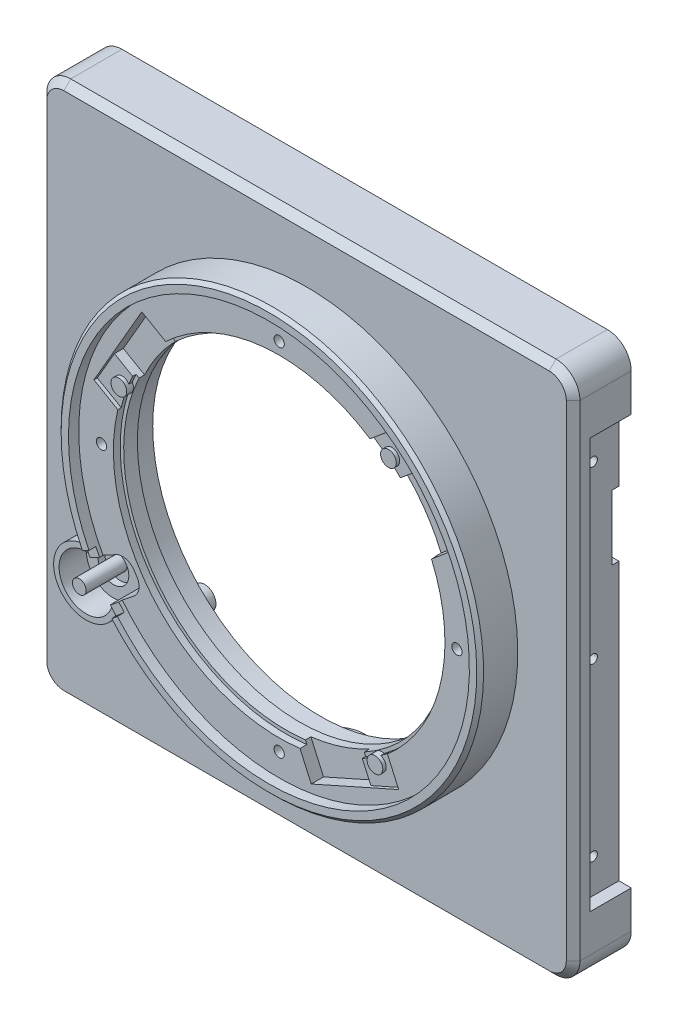
SolidWorks part; units mm, degrees
ref_plane "前视基准面" through (0, 0, 0) normal (0, 0, 1) x (1, 0, 0)
ref_plane "上视基准面" through (0, 0, 0) normal (0, 1, 0) x (1, 0, 0)
ref_plane "右视基准面" through (0, 0, 0) normal (1, 0, 0) x (0, 0, -1)
other "Configuration Table"
sketch "草图1" plane through (0, 0, 0) normal (0, 0, 1) x (1, 0, 0)
  line L1 (-39, -39) -> (39, -39)
  line L2 (-39, -39) -> (-39, 39)
  line L3 (-39, 39) -> (39, 39)
  line L4 (39, -39) -> (39, 39)
  line L5 (-39, -39) -> (39, 39) construction
  line L6 (-39, 39) -> (39, -39) construction
  circle A0 centre (0, 0) radius 23.75
  point P0 (0, 0)
  dimension "D2" = 47.5
  dimension "D1" = 78
extrude "凸台-拉伸1" add sketch "草图1" against normal blind 2
sketch "草图2" plane through (0, 0, 0) normal (0, 0, 1) x (1, 0, 0)
  circle A0 centre (0, 0) radius 23.75
  circle A1 centre (0, 0) radius 23.75 construction
  circle A2 centre (0, 0) radius 30.9
  dimension "D1" = 61.8
extrude "凸台-拉伸2" add sketch "草图2" along normal blind 4
sketch "草图3" plane through (0, 0, -2) normal (0, 0, -1) x (-1, 0, 0)
  line L1 (-39, -39) -> (39, -39)
  line L2 (-39, -39) -> (-39, 39)
  line L3 (-39, 39) -> (39, 39)
  line L4 (39, -39) -> (39, 39)
  line L5 (-39, -39) -> (39, 39) construction
  line L6 (-39, 39) -> (39, -39) construction
  line L7 (-37, -37) -> (37, -37)
  line L8 (-37, -37) -> (-37, 37)
  line L9 (-37, 37) -> (37, 37)
  line L10 (37, -37) -> (37, 37)
  line L11 (-37, -37) -> (37, 37) construction
  line L12 (-37, 37) -> (37, -37) construction
  line L13 (-37, 37) -> (-32, 37)
  line L14 (-37, 37) -> (-37, 32)
  line L15 (-37, 32) -> (-32, 32)
  line L16 (-32, 37) -> (-32, 32)
  line L17 (37, 37) -> (32, 37)
  line L18 (37, 37) -> (37, 32)
  line L19 (37, 32) -> (32, 32)
  line L20 (32, 37) -> (32, 32)
  line L21 (-37, -37) -> (-32, -37)
  line L22 (-37, -37) -> (-37, -32)
  line L23 (-37, -32) -> (-32, -32)
  line L24 (-32, -37) -> (-32, -32)
  line L25 (37, -37) -> (32, -37)
  line L26 (37, -37) -> (37, -32)
  line L27 (37, -32) -> (32, -32)
  line L28 (32, -37) -> (32, -32)
  line L29 (-35.5, 32) -> (-35.5, -32)
  point P0 (0, 0)
  point P7 (0, 0)
  line M23 (-39, 39) -> (-39, -39)
  line M24 (-39, -39) -> (39, -39)
  line M25 (39, -39) -> (39, 39)
  line M26 (39, 39) -> (-39, 39)
  dimension "D1" = 2
  dimension "D2" = 5
  dimension "D4" = 1.5
extrude "凸台-拉伸3" add sketch "草图3" along normal blind 6.5 contours L10 L7 L8 L9 M26 M23 M24 M25 | L16 L9 L8 L15 | L29 L15 L8 L23 | L7 L24 L23 L8 | L28 L7 L10 L27 | L9 L20 L19 L10 region at (37.8969, 0, -2) region at (34.5, -34.5, -2) region at (36.25, 0, -2) region at (-34.5, -34.5, -2) region at (34.5, 34.5, -2) region at (-34.5, 34.5, -2)
sketch "草图4" plane through (0, 0, 4) normal (0, 0, 1) x (1, 0, 0)
  line L0 (0, 26) -> (0, -26) construction
  line L1 (-26, 0) -> (26, 0) construction
  circle A0 centre (0, 0) radius 26 construction
  circle A1 centre (0, 26) radius 0.75
  circle A2 centre (26, 0) radius 0.75
  circle A3 centre (0, -26) radius 0.75
  circle A4 centre (-26, 0) radius 0.75
  dimension "D2" = 52
  dimension "D3" = 1.5
extrude "切除-拉伸1" cut sketch "草图4" against normal blind 5
sketch "草图5" plane through (0, 0, 4) normal (0, 0, 1) x (1, 0, 0)
  line L0 (-15.4397, 0) -> (13.8511, 0) construction
  line L1 (-27.9748, -13.7193) -> (-23.5593, -20.3904)
  line L2 (-23.5593, -20.3904) -> (0, 0) construction
  line L3 (0, 0) -> (-27.9748, -13.7193) construction
  line L4 (-25.7671, -17.0549) -> (0, 0) construction
  line L5 (-27.9748, -13.7193) -> (-26.8884, -13.1865)
  line L6 (-26.8884, -13.1865) -> (-26.2006, -14.2257)
  line L7 (-26.2006, -14.2257) -> (0, 0) construction
  line L8 (0, 0) -> (-23.3322, -18.5593) construction
  line L9 (-23.3322, -18.5593) -> (-22.6444, -19.5985)
  line L10 (-22.6444, -19.5985) -> (-23.5593, -20.3904)
  line L11 (-26.2006, -14.2257) -> (-23.8565, -12.953)
  line L12 (-21.2344, -13.6068) -> (-20.822, -14.2298)
  line L13 (-21.2448, -16.8989) -> (-23.3322, -18.5593)
  circle A0 centre (0, 0) radius 30.9 construction
  arc A1 (-20.822, -14.2298) -> (-21.2448, -16.8989) centre (-22.4898, -15.3336) cw
  arc A2 (-23.8565, -12.953) -> (-21.2344, -13.6068) centre (-22.9021, -14.7106) cw
  point P17 (-19.8105, -15.758)
  point P20 (-22.2459, -12.0785)
  dimension "D6" = 2
  dimension "D1" = 33.5
  dimension "D2" = 8
  dimension "D3" = 5
  dimension "D4" = 1.2
  dimension "D5" = 4.5
extrude "切除-拉伸2" cut sketch "草图5" against normal blind 4
sketch "草图8" plane through (0, 0, 4) normal (0, 0, 1) x (1, 0, 0)
  line L0 (-27.7433, -13.6058) -> (-26.3292, -12.9123)
  line L1 (-23.3644, -20.2217) -> (-22.1735, -19.191)
  circle A0 centre (0, 0) radius 30.9
  circle A1 centre (0, 0) radius 29.325
  arc A2 (-23.3644, -20.2217) -> (-27.7433, -13.6058) centre (0, 0) ccw construction
  line M27 (-27.7433, -13.6058) -> (-26.8884, -13.1865)
  line M35 (-22.6444, -19.5985) -> (-23.3644, -20.2217)
  arc M36 (-23.3644, -20.2217) -> (-27.7433, -13.6058) centre (0, 0) ccw
  dimension "D1" = 58.65
extrude "凸台-拉伸5" add sketch "草图8" along normal blind 1.5 contours A1 L1 L0 M35 M36 M27 region at (-6.7861, 29.2491, 4)
chamfer "倒角1" distance 0.5 angle 45 1 edges at (25.7671, 17.0549, 5.5)
sketch "草图9" plane through (0, 0, -2) normal (0, 0, -1) x (-1, 0, 0)
  line L1 (-19, -20) -> (19, -20) construction
  line L2 (-19, -20) -> (-19, 20) construction
  line L3 (-19, 20) -> (19, 20) construction
  line L4 (19, -20) -> (19, 20) construction
  line L5 (-19, -20) -> (19, 20) construction
  line L6 (-19, 20) -> (19, -20) construction
  circle A0 centre (-19, -20) radius 0.8
  circle A1 centre (-19, -20) radius 1.65
  circle A4 centre (19, 20) radius 0.8
  circle A5 centre (19, 20) radius 1.65
  circle A6 centre (19, -20) radius 0.8
  circle A7 centre (19, -20) radius 1.65
  point P0 (0, 0)
  dimension "D2" = 1.6
  dimension "D3" = 3.3
  dimension "D1" = 38
  dimension "D4" = 40
extrude "凸台-拉伸6" add sketch "草图9" along normal blind 2.1
extrude "切除-拉伸4" cut sketch "草图9<2>" against normal blind 2 contours A4 | A0 | A6 region at (19, -20, -2) region at (-19, 20, -2) region at (-19, -20, -2)
sketch "草图9<2>" plane through (0, 0, -2) normal (0, 0, -1) x (-1, 0, 0) same geometry as "草图9"
sketch "草图10" plane through (0, 0, -8.5) normal (0, 0, -1) x (-1, 0, 0)
  line L0 (39, 39) -> (-39, 39) construction
  line L1 (34.5, -34.5) -> (-34.5, -34.5) construction
  line L2 (34.5, -34.5) -> (34.5, 34.5) construction
  line L3 (34.5, 34.5) -> (-34.5, 34.5) construction
  line L4 (-34.5, -34.5) -> (-34.5, 34.5) construction
  line L5 (34.5, -34.5) -> (-34.5, 34.5) construction
  line L6 (34.5, 34.5) -> (-34.5, -34.5) construction
  circle A0 centre (-34.5, 34.5) radius 0.8
  circle A1 centre (34.5, 34.5) radius 0.8
  circle A2 centre (34.5, -34.5) radius 0.8
  circle A3 centre (-34.5, -34.5) radius 0.8
  point P0 (0, 0)
  dimension "D2" = 1.6
  dimension "D1" = 4.5
extrude "切除-拉伸5" cut sketch "草图10" against normal blind 4
sketch "草图18" plane through (0, -39, 0) normal (0, -1, 0) x (1, 0, 0)
  line L0 (39, -8.5) -> (-39, -8.5) construction
  line L1 (-39, 0) -> (39, 0) construction
  circle A0 centre (0, -4.25) radius 4.25
  circle A1 centre (0, -4.25) radius 2.5527
  dimension "D1" = 5.1054
extrude "凸台-拉伸9" add sketch "草图18" against normal blind 9 contours A1 | A0 A1 region at (-4.1298, -39, -4.25) region at (0, -39, -4.25)
extrude "切除-拉伸9" cut sketch "草图18<4>" against normal blind 7.5 contours A1 region at (0, -39, -4.25)
sketch "草图18<4>" plane through (0, -39, 0) normal (0, -1, 0) x (1, 0, 0) same geometry as "草图18"
sketch "草图30" plane through (0, 0, 0) normal (0, 0, 1) x (1, 0, 0)
  line L0 (-22.39, -14.8196) -> (0, 0) construction
  line L1 (-26.8884, -13.1865) -> (-28.4451, -13.9499)
  line L2 (-26.2006, -14.2257) -> (-27.3486, -14.8491)
  line L3 (-23.3322, -18.5593) -> (-24.3546, -19.3725)
  line L4 (-22.6444, -19.5985) -> (-23.9553, -20.7332)
  line L5 (-22.6444, -19.5985) -> (-23.3322, -18.5593)
  line L6 (-23.3644, -20.2217) -> (-22.6444, -19.5985) construction
  line L7 (-23.3322, -18.5593) -> (-21.2448, -16.8989) construction
  line L8 (-23.8565, -12.953) -> (-26.2006, -14.2257) construction
  line L9 (-27.2944, -13.3856) -> (-26.3292, -12.9123) construction
  line L10 (-26.8884, -13.1865) -> (-26.2006, -14.2257)
  line L11 (-20.822, -14.2298) -> (-21.2344, -13.6068) construction
  line L12 (-20.822, -14.2298) -> (-21.2344, -13.6068) construction
  circle A0 centre (-28.2462, -18.6958) radius 4.75
  circle A2 centre (-28.2462, -18.6958) radius 3.95
  point P3 (-21.0282, -13.9183)
  line M13 (-26.8884, -13.1865) -> (-27.7433, -13.6058)
  line M15 (-23.3644, -20.2217) -> (-22.6444, -19.5985)
  line M16 (-22.6444, -19.5985) -> (-23.3322, -18.5593)
  line M22 (-26.2006, -14.2257) -> (-26.8884, -13.1865)
  dimension "D2" = 9.5
  dimension "D3" = 7.9
  dimension "D1" = 33.873
extrude "凸台-拉伸10" add sketch "草图30" along normal blind 4 contours A0 L2 L1 M22 M13 | A0 L0 A2 L2 | L0 A0 L3 A2 | A0 L4 L3 M15 M16 region at (-27.1202, -13.7897, 0) region at (-27.418, -14.155, 0) region at (-23.2902, -19.5762, 0)
sketch "草图31" plane through (0, 0, 0) normal (0, 0, 1) x (1, 0, 0)
  circle A0 centre (-28.2462, -18.6958) radius 1
  circle A1 centre (-28.2462, -18.6958) radius 2.25
  dimension "D1" = 2
  dimension "D2" = 4.5
extrude "切除-拉伸19" cut sketch "草图31" against normal blind 1
sketch "草图32" plane through (0, 0, 0) normal (0, 0, 1) x (1, 0, 0)
  circle A0 centre (-28.2462, -18.6958) radius 1
  circle A1 centre (-28.2462, -18.6958) radius 1 construction
extrude "凸台-拉伸11" add sketch "草图32" along normal blind 5
sketch "草图33" plane through (0, 0, 4) normal (0, 0, 1) x (1, 0, 0)
  line L0 (-26.3292, -12.9123) -> (-27.7433, -13.6058)
  line L1 (-27.1554, -14.7442) -> (-25.7713, -13.9927)
  line L2 (-23.8565, -12.953) -> (-27.3486, -14.8491) construction
  line L3 (-23.8565, -12.953) -> (-27.3486, -14.8491) construction
  line L4 (-24.1826, -19.2357) -> (-22.95, -18.2552)
  line L5 (-24.3546, -19.3725) -> (-21.2448, -16.8989) construction
  line L6 (-22.1735, -19.191) -> (-23.3644, -20.2217)
  circle A0 centre (0, 0) radius 29.325
  circle A1 centre (0, 0) radius 30.9
  line M3 (-26.3292, -12.9123) -> (-27.7433, -13.6058)
  line M7 (-23.3644, -20.2217) -> (-22.1735, -19.191)
  line M10 (-27.3486, -14.8491) -> (-23.8565, -12.953)
  line M14 (-21.2448, -16.8989) -> (-24.3546, -19.3725)
extrude "凸台-拉伸12" add sketch "草图33" along normal blind 0.5 contours A1 A0 M3 M10 | A1 A0 M14 M7 region at (-26.7598, -13.8189, 4) region at (-23.1762, -19.233, 4)
fillet "圆角5" radius 1 2 edges at (-3.6056, -33.5, -2) (3.6056, -33.5, -2)
fillet "圆角2" radius 1.5 12 edges at (32, -37, -5.25) (-32, -37, -5.25) (-32, -32, -5.25) (-37, -32, -5.25) (-37, 32, -5.25) (-32, 37, -5.25) (32, -32, -5.25) (-32, 32, -5.25) (32, 37, -5.25) (32, 32, -5.25) (35.5, 32, -5.25) (35.5, -32, -5.25)
fillet "圆角3" radius 3.5 4 edges at (39, -39, -4.25) (-39, -39, -4.25) (-39, 39, -4.25) (39, 39, -4.25)
chamfer "倒角2" distance 1 angle 45 8 edges at (0, -39, 0) (37.9749, -37.9749, 0) (-37.9749, -37.9749, 0) (39, 0, 0) (-39, 0, 0) (37.9749, 37.9749, 0) (-37.9749, 37.9749, 0) (0, 39, 0)
sketch "草图11" plane through (0, 0, 4) normal (0, 0, 1) x (1, 0, 0)
  circle A0 centre (0, 0) radius 24.25
  dimension "D1" = 48.5
extrude "切除-拉伸6" cut sketch "草图11" against normal blind 1
sketch "草图19" plane through (39, 0, 0) normal (-1, 0, 0) x (0, 0, 1)
  line L0 (-8.5, -35.5) -> (-8.5, 35.5) construction
  line L1 (-8.5, 30) -> (-2.5, 30)
  line L2 (-8.5, 30) -> (-8.5, -30)
  line L3 (-8.5, -30) -> (-2.5, -30)
  line L4 (-2.5, 30) -> (-2.5, -30)
  line L5 (-10.4781, 0) -> (-27.7758, 0) construction
  dimension "D1" = 6
  dimension "D2" = 60
extrude "切除-拉伸10" cut sketch "草图19" along normal blind 1.8
sketch "草图12" plane through (0, 0, -8.5) normal (0, 0, -1) x (-1, 0, 0)
  line L0 (-30.5, 37) -> (30.5, 37) construction
  line L1 (-14.5, 37) -> (14.5, 37)
  line L2 (-14.5, 37) -> (-14.5, 38)
  line L3 (-14.5, 38) -> (14.5, 38)
  line L4 (14.5, 37) -> (14.5, 38)
  line L10 (-30.5, -37) -> (-5.099, -37) construction
  line L11 (14.5, -37) -> (-14.5, -37)
  line L12 (14.5, -37) -> (14.5, -38)
  line L13 (14.5, -38) -> (-14.5, -38)
  line L14 (-14.5, -37) -> (-14.5, -38)
  line L20 (0, -4.6052) -> (0, 11.8131) construction
  line L21 (9.1859, 0) -> (-14.9207, 0) construction
  line L22 (-3.5, -37) -> (-3.5, -38)
  line L23 (3.5, -37) -> (3.5, -38)
  line M27 (30.5, -37) -> (0, -37)
  line M39 (-30.5, 37) -> (30.5, 37)
  dimension "D1" = 29
  dimension "D2" = 1
  dimension "D3" = 7
extrude "切除-拉伸7" cut sketch "草图12" against normal blind 1 contours L22 L11 L14 L13 | L23 L13 L12 M27 | L4 L3 L2 M39
sketch "草图21" plane through (0, 0, -2) normal (0, 0, -1) x (-1, 0, 0)
  circle A0 centre (0, 0) radius 24.5
  dimension "D1" = 49
extrude "切除-拉伸12" cut sketch "草图21" against normal blind 3
sketch "草图22" plane through (0, 0, 0) normal (0, 0, 1) x (1, 0, 0)
  text T0 "Sitina" font "Corbel" height 3.5
  text T1 "S1" font "Sylfaen" height 3.5
sketch "草图23" plane through (0, 0, -8.5) normal (0, 0, -1) x (-1, 0, 0)
  line L1 (-35.5, 20) -> (-37.2, 20)
  line L2 (-35.5, 20) -> (-35.5, 10.5)
  line L3 (-35.5, 10.5) -> (-37.2, 10.5)
  line L4 (-37.2, 20) -> (-37.2, 10.5)
  line L5 (-37.2, -30) -> (-37.2, 30) construction
  line L6 (-35.5, 30.5) -> (-35.5, -30.5) construction
  dimension "D1" = 9.5
  dimension "D2" = 10.5
extrude "切除-拉伸14" cut sketch "草图23" against normal blind 1
sketch "草图24" plane through (37.2, 0, 0) normal (1, 0, 0) x (0, 0, -1)
  line L0 (4.7, -23.516) -> (4.7, -0.4558) construction
  line L3 (4.7, -25) -> (4.7, 0) construction
  line L4 (8.5, -30) -> (8.5, -35.5) construction
  line L5 (8.5, -39) -> (1, -39) construction
  circle A0 centre (4.7, -25) radius 0.65
  circle A1 centre (4.7, 0) radius 0.65
  circle A2 centre (4.7, 25) radius 0.65
  point P6 (8.5, -32.75)
  dimension "D2" = 1.3
  dimension "D1" = 3.8
  dimension "D3" = 14
  dimension "D5" = 25
  dimension "D4" = 3
extrude "切除-拉伸15" cut sketch "草图24" against normal blind 4.75
sketch "草图26" plane through (-39, 0, 0) normal (1, 0, 0) x (0, 0, -1)
  line L0 (8.5, 35.5) -> (8.5, 30) construction
  line L1 (5.8, -30) -> (7.2, -30)
  line L2 (5.8, -30) -> (5.8, -18.5)
  line L3 (5.8, -18.5) -> (7.2, -18.5)
  line L4 (7.2, -30) -> (7.2, -18.5)
  line L5 (1, -35.5) -> (8.5, -35.5) construction
  line L6 (12.7, 2.7) -> (7.7, 2.7) construction
  line L7 (12.7, 0.6) -> (7.7, 0.6)
  line L8 (12.7, 4.8) -> (7.7, 4.8)
  line L9 (8.5, 29.5) -> (8.5, 20.4)
  line L12 (8.5, 35.5) -> (1, 35.5) construction
  line L13 (8.5, 20.4) -> (6.3, 20.4)
  line L14 (8.5, 29.5) -> (6.3, 29.5)
  line L15 (5.1, 28.3) -> (5.1, 21.6)
  line L17 (8.5, 14) -> (5.1, 14)
  line L18 (8.5, 14) -> (8.5, 6)
  line L19 (8.5, 6) -> (5.1, 6)
  line L20 (5.1, 14) -> (5.1, 6)
  circle A0 centre (9, -10.2) radius 4.25
  arc A1 (12.7, 0.6) -> (12.7, 4.8) centre (12.7, 2.7) ccw
  arc A2 (7.7, 4.8) -> (7.7, 0.6) centre (7.7, 2.7) ccw
  arc A5 (6.3, 29.5) -> (5.1, 28.3) centre (6.3, 28.3) ccw
  arc A6 (6.3, 20.4) -> (5.1, 21.6) centre (6.3, 21.6) cw
  point P10 (10.2, 2.7)
  dimension "D7" = 8.5
  dimension "D9" = 2.1
  dimension "D15" = 1.2
  dimension "D1" = 11.5
  dimension "D2" = 1.4
  dimension "D3" = 1.3
  dimension "D4" = 5.5
  dimension "D5" = 25.3
  dimension "D6" = 0.5
  dimension "D8" = 38.2
  dimension "D10" = 0.8
  dimension "D11" = 5
  dimension "D12" = 6
  dimension "D13" = 9.1
  dimension "D14" = 3.4
  dimension "D16" = 21.5
  dimension "D17" = 8
  dimension "D18" = 3.4
extrude "切除-拉伸17" cut sketch "草图26" along normal blind 10
sketch "草图29" plane through (0, 0, -2) normal (0, 0, -1) x (-1, 0, 0)
  line L0 (0, 6.6658) -> (0, 18.0542) construction
  line L1 (6.3625, 0) -> (19.1145, 0) construction
  circle A0 centre (-15, 22) radius 0.8
  circle A1 centre (15, -22) radius 0.8
  dimension "D1" = 1.6
  dimension "D2" = 15
  dimension "D3" = 15
  dimension "D4" = 22
  dimension "D5" = 22
extrude "切除-拉伸18" cut sketch "草图29" against normal blind 3
fillet "圆角6" radius 0.5 2 edges at (-27.7433, -13.6058, 2) (-23.3644, -20.2217, 2)
sketch "草图34" plane through (0, 0, 4) normal (0, 0, 1) x (1, 0, 0)
  line L0 (15.2413, -17.0225) -> (2.4517, -22.7168)
  line L1 (2.4517, -22.7168) -> (4.6888, -27.7413)
  line L2 (4.6888, -27.7413) -> (17.4784, -22.047)
  line L3 (17.4784, -22.047) -> (15.2413, -17.0225)
  line L4 (0, -1000) -> (0, 49000) construction
  line L5 (0, 0) -> (8.8465, -19.8696) construction
  line L6 (10.6736, -19.0561) -> (12.9107, -24.0806)
  line L7 (12.162, 19.3429) -> (21.161, 8.6183)
  line L8 (21.161, 8.6183) -> (25.3742, 12.1537)
  line L9 (25.3742, 12.1537) -> (16.3752, 22.8783)
  line L10 (16.3752, 22.8783) -> (12.162, 19.3429)
  line L11 (-15.3361, 16.9372) -> (-22.3361, 4.8128)
  line L12 (-22.3361, 4.8128) -> (-27.0992, 7.5628)
  line L13 (-27.0992, 7.5628) -> (-20.0992, 19.6872)
  line L14 (-20.0992, 19.6872) -> (-15.3361, 16.9372)
  line L15 (-24.5992, 11.8929) -> (-19.8361, 9.1429)
  line L16 (15.3759, 15.5127) -> (19.5891, 19.0481)
  line L17 (-18.8361, 10.875) -> (0, 0)
  line L18 (0, 0) -> (16.6615, 13.9806)
  circle A0 centre (0, 0) radius 21.75 construction
  point P5 (8.8465, -19.8696)
  point P19 (-18.8361, 10.875)
  point P22 (16.6615, 13.9806)
  circle M8 centre (0, 0) radius 24.25
  dimension "D1" = 43.5
  dimension "D2" = 14
  dimension "D3" = 5.5
  dimension "D4" = 24
  dimension "D5" = 5
  dimension "D6" = 5
  dimension "D7" = 5
  dimension "D8" = 60
  dimension "D9" = 50
extrude "切除-拉伸20" cut sketch "草图34" against normal blind 0.5 contours L6 L2 L3 M8 | L0 L6 L3 M8 | L16 L9 L10 M8 | L7 L16 L10 M8 | L15 L13 L12 M8 | L15 L12 L11 M8 region at (13.2013, -19.0643, 4) region at (14.5891, -21.424, 4) region at (-21.8858, 7.6638, 4) region at (-24.3955, 8.7571, 4) region at (16.5728, 19.9292, 4) region at (14.687, 17.9447, 4)
extrude "切除-拉伸21" cut sketch "草图34<3>" against normal blind 1.8 contours L6 L0 L1 M8 | L6 L1 L2 M8 | L13 L15 L14 M8 | L15 L11 L14 M8 | L16 L8 L9 M8 | L16 L7 L8 M8 region at (7.314, -21.7939, 4) region at (7.9313, -24.492, 4) region at (21.357, 14.375, 4) region at (18.9336, 13.0379, 4) region at (-18.7273, 13.3326, 4) region at (-20.8126, 15.1525, 4)
sketch "草图34<3>" plane through (0, 0, 4) normal (0, 0, 1) x (1, 0, 0) same geometry as "草图34"
sketch "草图35" plane through (0, 0, 3) normal (0, 0, 1) x (1, 0, 0)
  line L0 (17.4784, -22.047) -> (15.8383, -18.3633) construction
  line L1 (12.9107, -24.0806) -> (17.4784, -22.047) construction
  line L2 (25.3742, 12.1537) -> (16.3752, 22.8783) construction
  line L3 (-27.0992, 7.5628) -> (-20.0992, 19.6872) construction
  line L4 (-23.6071, 5.5467) -> (-27.0992, 7.5628) construction
  line L5 (16.3752, 22.8783) -> (13.2863, 20.2864) construction
  circle A0 centre (14.005, -20.6379) radius 1.15
  circle A1 centre (15.9781, 19.151) radius 1.15
  circle A2 centre (-23.4609, 8.4645) radius 1.15
  dimension "D1" = 2.3
  dimension "D2" = 2.6
  dimension "D3" = 2.7
  dimension "D4" = 2.7
  dimension "D5" = 2.7
  dimension "D6" = 2.6
  dimension "D7" = 2.6
extrude "凸台-拉伸13" add sketch "草图35" along normal blind 1
sketch "草图36" plane through (0, 0, -8.5) normal (0, 0, -1) x (-1, 0, 0)
  line L0 (39, -35.5) -> (39, -14.4205) construction
  line L1 (-1040.6187, -24.25) -> (48959.3813, -24.25) construction
  line L2 (-39, -30) -> (-39, -18.5) construction
  circle A0 centre (44, -24.25) radius 5.8
  point P5 (-39, -24.25)
  point P7 (0, 0)
  point P8 (43.9185, -22.4602)
  dimension "D2" = 11.6
  dimension "D1" = 5
extrude "切除-拉伸22" cut sketch "草图36" against normal blind 4
fillet "圆角7" radius 0.5 1 edges at (-38.2, -24.25, -4.5)
